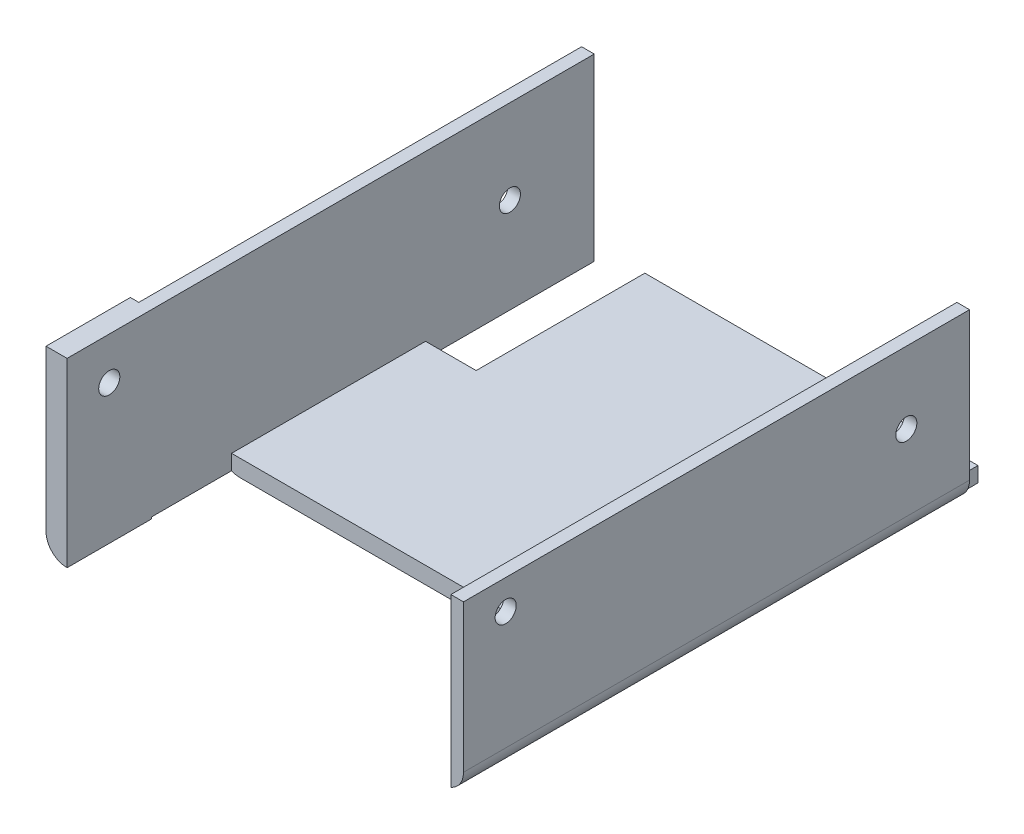
SolidWorks part; units mm, degrees
ref_plane "Alzado" through (0, 0, 0) normal (0, 0, 1) x (1, 0, 0)
ref_plane "Planta" through (0, 0, 0) normal (0, 1, 0) x (1, 0, 0)
ref_plane "Vista lateral" through (0, 0, 0) normal (1, 0, 0) x (0, 0, -1)
sketch "Croquis2" plane through (0, 0, 0) normal (0, 0, 1) x (1, 0, 0)
  line L0 (-63.9818, 0) -> (70.0607, 0) construction
  line L1 (56.4756, 13.4229) -> (56.4756, -26.5771)
  line L2 (56.4756, -26.5771) -> (-40.5244, -26.5771)
  line L3 (-40.5244, -26.5771) -> (-40.5244, 16.4229)
  line L4 (-40.5244, 16.4229) -> (-37.5244, 16.4229)
  line L5 (56.4756, 13.4229) -> (53.4756, 13.4229)
  line L6 (-37.5244, -22.5771) -> (53.4756, -22.5771)
  line L7 (-37.5244, 16.4229) -> (-37.5244, -22.5771)
  line L8 (53.4756, 13.4229) -> (53.4756, -22.5771)
  dimension "D1" = 97
  dimension "D2" = 43
  dimension "D3" = 40
  dimension "D4" = 3
  dimension "D5" = 3
  dimension "D6" = 4
extrude "Saliente-Extruir1" add sketch "Croquis2" along normal blind 125
sketch "Croquis3" plane through (0, -22.5771, 0) normal (0, 1, 0) x (1, 0, 0)
  line L9 (53.4756, 0) -> (-37.5244, 0) construction
  line L10 (53.4756, 0) -> (57.4756, 0)
  line L11 (53.4756, 0) -> (53.4756, -5)
  line L12 (53.4756, -5) -> (57.4756, -5)
  line L13 (57.4756, 0) -> (57.4756, -5)
  line L14 (-37.5244, 0) -> (-25.5244, 0)
  line L15 (-37.5244, 0) -> (-37.5244, -40)
  line L16 (-37.5244, -40) -> (-25.5244, -40)
  line L17 (-25.5244, 0) -> (-25.5244, -40)
  line L19 (-37.5244, -125) -> (-37.5244, 0) construction
  point P1 (-31.5244, 0)
  dimension "D4" = 5
  dimension "D5" = 4
  dimension "D6" = 40
  dimension "D7" = 12
extrude "Cortar-Extruir1" cut sketch "Croquis3" along normal blind 125 and the other way blind 125
sketch "Croquis4" plane through (0, -22.5771, 0) normal (0, 1, 0) x (1, 0, 0)
  line L0 (53.4756, -125) -> (53.4756, -5) construction
  line L1 (-37.5244, -125) -> (53.4756, -125)
  line L2 (-37.5244, -125) -> (-37.5244, -86)
  line L3 (-37.5244, -86) -> (53.4756, -86)
  line L4 (53.4756, -125) -> (53.4756, -86)
  dimension "D1" = 39
extrude "Cortar-Extruir2" cut sketch "Croquis4" against normal blind 125
sketch "Croquis5" plane through (-40.5244, 0, 0) normal (-1, 0, 0) x (0, 0, 1)
  line L0 (125, -26.5771) -> (0, -26.5771) construction
  line L1 (125, 16.4229) -> (105, 16.4229)
  line L2 (125, 16.4229) -> (125, -26.5771)
  line L3 (125, -26.5771) -> (105, -26.5771)
  line L4 (105, 16.4229) -> (105, -26.5771)
  dimension "D1" = 20
extrude "Saliente-Extruir2" add sketch "Croquis5" along normal blind 2
sketch "Croquis6" plane through (-40.5244, 0, 0) normal (-1, 0, 0) x (0, 0, 1)
  line L1 (105, 16.4229) -> (0, 16.4229) construction
  line L2 (0, 16.4229) -> (0, -26.5771) construction
  circle A0 centre (20, -3.5771) radius 2.5
  dimension "D1" = 20
  dimension "D3" = 5
  dimension "D2" = 20
extrude "Cortar-Extruir3" cut sketch "Croquis6" against normal blind 124
sketch "Croquis7" plane through (-42.5244, 0, 0) normal (-1, 0, 0) x (0, 0, 1)
  line L0 (125, 16.4229) -> (105, 16.4229) construction
  line L1 (125, -26.5771) -> (125, 16.4229) construction
  circle A0 centre (115, 6.4229) radius 2.5
  dimension "D3" = 5
  dimension "D1" = 10
  dimension "D2" = 10
extrude "Cortar-Extruir4" cut sketch "Croquis7" against normal blind 124
fillet "Redondeo1" radius 5 2 edges at (56.4756, -26.5771, 65) (-40.5244, -26.5771, 52.5)
fillet "Redondeo2" radius 5 1 edges at (-42.5244, -26.5771, 115)
